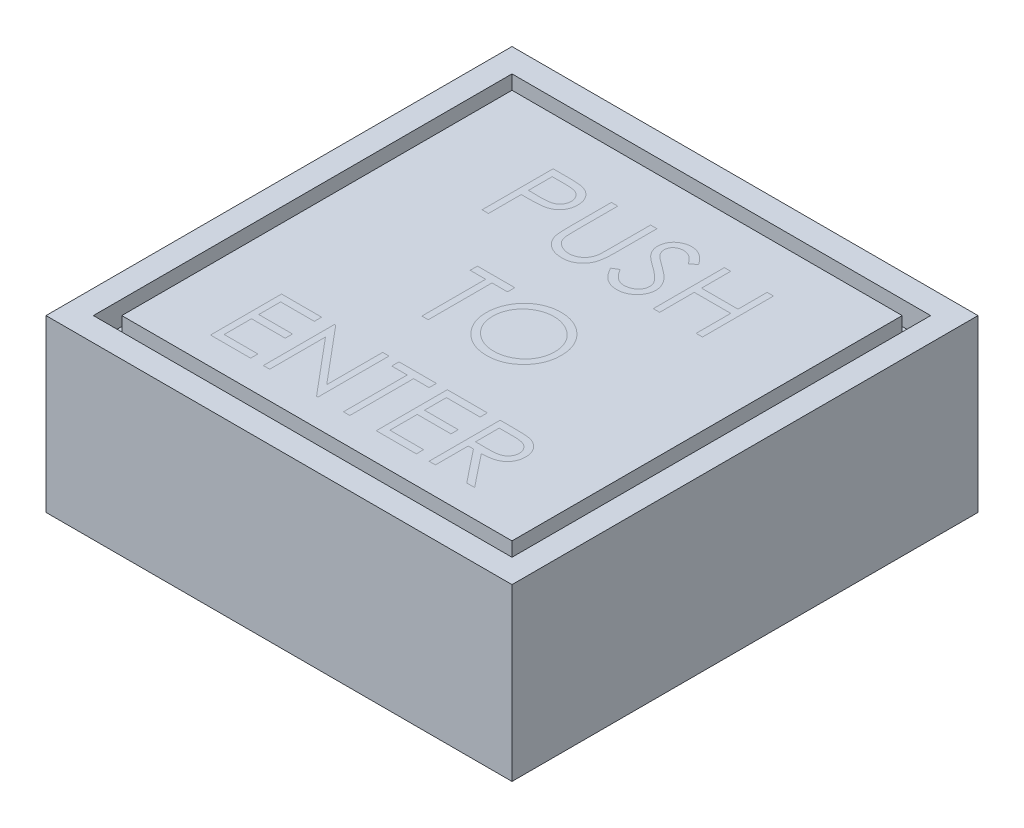
SolidWorks part; units mm, degrees
material "Stainless Steel (ferritic)"
ref_plane "Front Plane" through (0, 0, 0) normal (0, 0, 1) x (1, 0, 0)
ref_plane "Back of Button Plane" through (0, 0, 0) normal (0, 1, 0) x (1, 0, 0)
ref_plane "Right Plane" through (0, 0, 0) normal (1, 0, 0) x (0, 0, -1)
sketch "Sketch1" plane through (0, 0, 0) normal (0, 1, 0) x (1, 0, 0)
  line L1 (0, 0) -> (124.968, 0)
  line L2 (0, 0) -> (0, 124.968)
  line L3 (0, 124.968) -> (124.968, 124.968)
  line L4 (124.968, 0) -> (124.968, 124.968)
  dimension "D1" = 124.968
  dimension "D2" = 124.968
extrude "Boss-Extrude1" add sketch "Sketch1" along normal blind 45.72
sketch "Sketch4" plane through (0, 45.72, 0) normal (0, 1, 0) x (1, 0, 0)
  line L8 (6.35, 118.618) -> (6.35, 6.35)
  line L9 (6.35, 6.35) -> (118.618, 6.35)
  line L10 (118.618, 6.35) -> (118.618, 118.618)
  line L11 (118.618, 118.618) -> (6.35, 118.618)
  line L12 (6.35, 118.618) -> (6.35, 6.35)
  line L13 (6.35, 6.35) -> (118.618, 6.35)
  line L14 (118.618, 6.35) -> (118.618, 118.618)
  line L15 (118.618, 118.618) -> (6.35, 118.618)
  dimension "D1" = 6.35
extrude "Cut-Extrude1" cut sketch "Sketch4" against normal blind 6.35
sketch "Sketch6" plane through (0, 39.37, 0) normal (0, 1, 0) x (1, 0, 0)
  line L8 (114.808, 10.16) -> (114.808, 114.808)
  line L9 (10.16, 10.16) -> (114.808, 10.16)
  line L10 (10.16, 114.808) -> (10.16, 10.16)
  line L11 (114.808, 114.808) -> (10.16, 114.808)
  line L12 (114.808, 10.16) -> (114.808, 114.808)
  line L13 (10.16, 10.16) -> (114.808, 10.16)
  line L14 (10.16, 114.808) -> (10.16, 10.16)
  line L15 (114.808, 114.808) -> (10.16, 114.808)
  dimension "D1" = 3.81
extrude "Boss-Extrude2" add sketch "Sketch6" along normal blind 6.35
sketch "Sketch11" plane through (0, 45.72, 0) normal (0, 1, 0) x (1, 0, 0)
  text T0 " PUSH \r\n   TO\r\nENTER" font "Century Gothic" height in points 72
  point P1 (0, 0)
  point P2 (0, 0)
wrap "Wrap1" sketch "Sketch11" wrap type scribe source sketch "Sketch11" face at (62.484, 45.72, -62.484)
